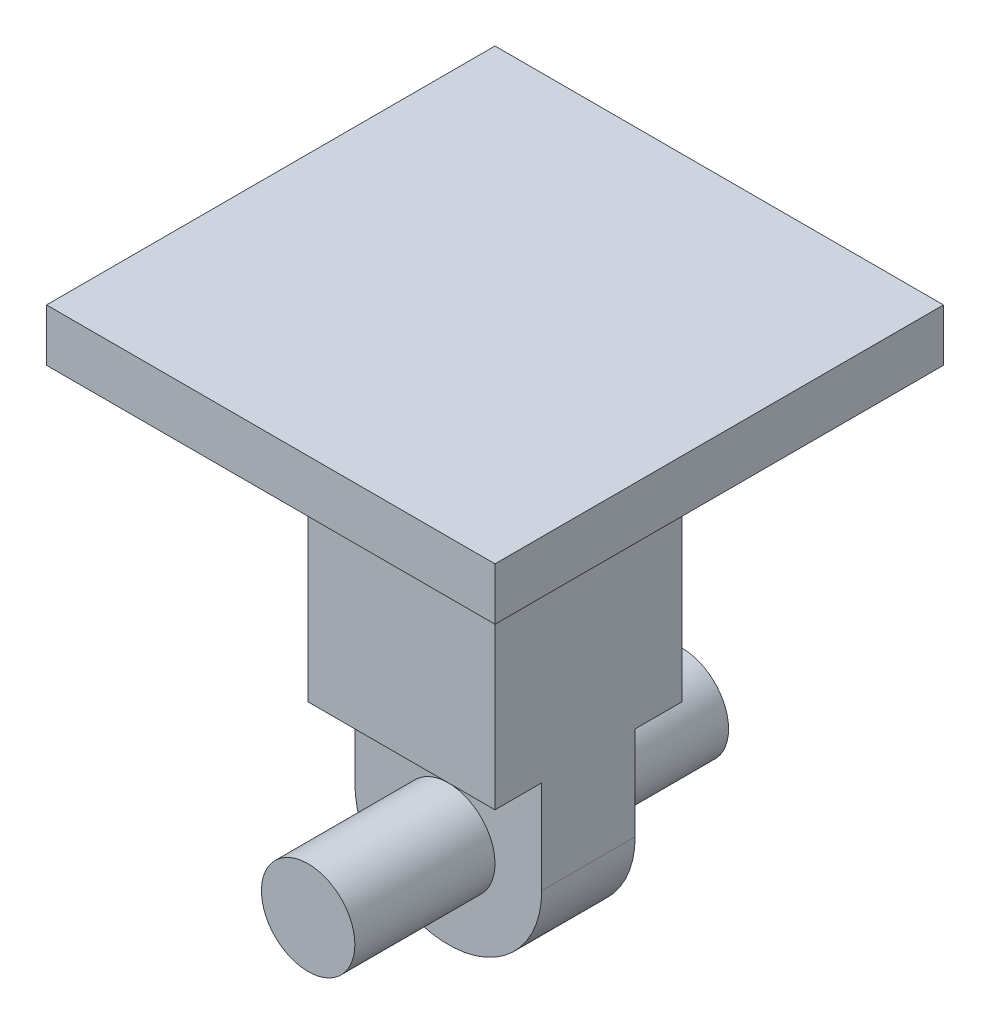
SolidWorks part; units mm, degrees
ref_plane "前视基准面" through (0, 0, 0) normal (0, 0, 1) x (1, 0, 0)
ref_plane "上视基准面" through (0, 0, 0) normal (0, 1, 0) x (1, 0, 0)
ref_plane "右视基准面" through (0, 0, 0) normal (1, 0, 0) x (0, 0, -1)
other "Configuration Table"
sketch "草图1" plane through (0, 0, 0) normal (0, 1, 0) x (1, 0, 0)
  line L1 (-30, -30) -> (30, -30)
  line L2 (-30, -30) -> (-30, 30)
  line L3 (-30, 30) -> (30, 30)
  line L4 (30, -30) -> (30, 30)
  line L5 (-30, -30) -> (30, 30) construction
  line L6 (-30, 30) -> (30, -30) construction
  point P0 (0, 0)
  dimension "D1" = 60
  dimension "D2" = 60
extrude "凸台-拉伸1" add sketch "草图1" along normal blind 7
sketch "草图3" plane through (0, 0, 0) normal (0, 1, 0) x (1, 0, 0)
  line L1 (-12.5, -12.5) -> (12.5, -12.5)
  line L2 (-12.5, -12.5) -> (-12.5, 12.5)
  line L3 (-12.5, 12.5) -> (12.5, 12.5)
  line L4 (12.5, -12.5) -> (12.5, 12.5)
  line L5 (-12.5, -12.5) -> (12.5, 12.5) construction
  line L6 (-12.5, 12.5) -> (12.5, -12.5) construction
  point P0 (0, 0)
  dimension "D1" = 25
  dimension "D2" = 25
extrude "凸台-拉伸2" add sketch "草图3" against normal blind 51.5
sketch "草图4" plane through (0, 0, 0) normal (0, 0, 1) x (1, 0, 0)
  line L0 (-12.5, -51.5) -> (12.5, -51.5) construction
  line L1 (12.5, -51.5) -> (-12.5, -51.5)
  arc A0 (-12.5, -51.5) -> (12.5, -51.5) centre (0, -51.5) ccw
extrude "凸台-拉伸3" add sketch "草图4" against normal up to surface (12.5 mm away) from surface up to face at (0, -25.75, -12.5) starting at face at (0, -25.75, 12.5)
sketch "草图7" plane through (0, 0, 0) normal (0, 1, 0) x (1, 0, 0)
  line L0 (12.5, -12.5) -> (12.5, 12.5) construction
  line L5 (-12.5, 12.5) -> (12.5, 12.5)
  line L6 (-12.5, 12.5) -> (-12.5, 6.25)
  line L7 (-12.5, 6.25) -> (12.5, 6.25)
  line L8 (12.5, 12.5) -> (12.5, 6.25)
  line L10 (-12.5, -12.5) -> (12.5, -12.5)
  line L11 (-12.5, -12.5) -> (-12.5, -6.25)
  line L12 (-12.5, -6.25) -> (12.5, -6.25)
  line L13 (12.5, -12.5) -> (12.5, -6.25)
  dimension "D1" = 6.25
  dimension "D2" = 6.25
extrude "切除-拉伸3" cut sketch "草图7" against normal blind 12.5 and the other way blind 12.5 from vertex starting at point (12.5, -51.5, 12.5)
sketch "草图8" plane through (0, 0, 0) normal (0, 0, 1) x (1, 0, 0)
  arc A0 (-12.5, -51.5) -> (12.5, -51.5) centre (0, -51.5) ccw construction
  arc A1 (-12.5, -51.5) -> (12.5, -51.5) centre (0, -51.5) ccw construction
  circle A2 centre (0, -51.5) radius 6.25
  dimension "D1" = 12.5
extrude "凸台-拉伸4" add sketch "草图8" against normal blind 25 and the other way blind 25
sketch "草图9" plane through (0, 0, 0) normal (1, 0, 0) x (0, 0, -1)
  line L0 (-75, -51.5) -> (75, -51.5)
  line L3 (25, -57.75) -> (25, -45.25) construction
  line L4 (25, -57.75) -> (25, -45.25) construction
  point P3 (0, -51.5)
  point P7 (25, -51.5)
  dimension "D1" = 150
